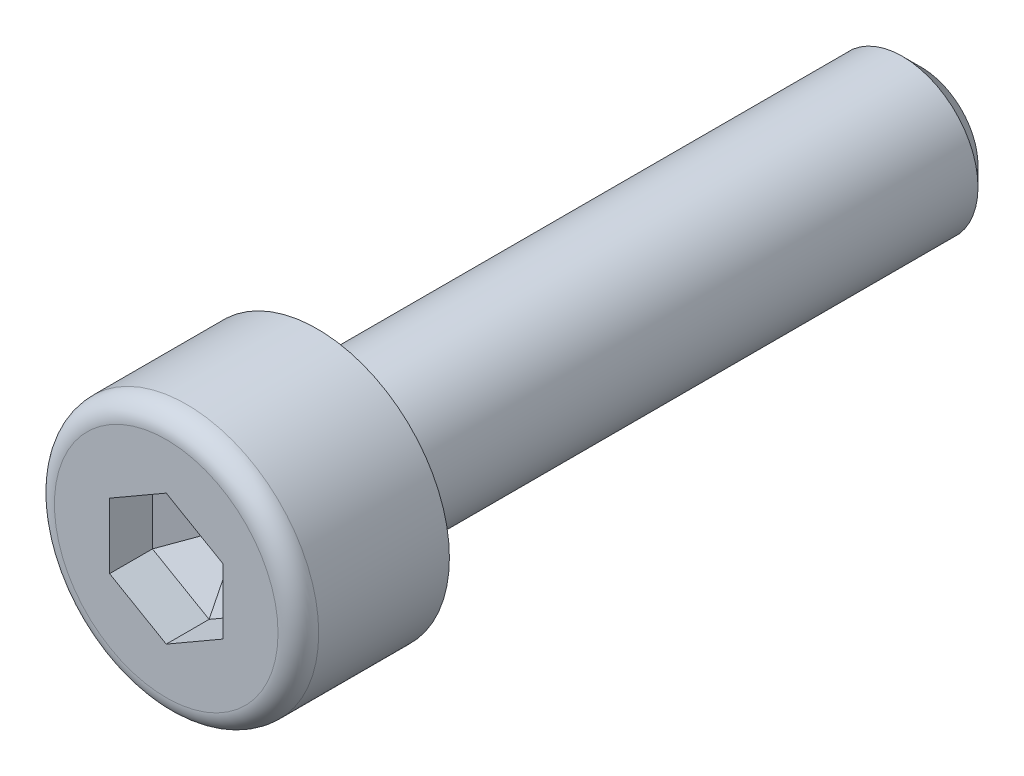
SolidWorks part; units mm, degrees
material "普通碳钢"
ref_plane "前视基准面" through (0, 0, 0) normal (0, 0, 1) x (1, 0, 0)
ref_plane "上视基准面" through (0, 0, 0) normal (0, 1, 0) x (1, 0, 0)
ref_plane "右视基准面" through (0, 0, 0) normal (1, 0, 0) x (0, 0, -1)
sketch "草图1" plane through (0, 0, 0) normal (0, 0, 1) x (1, 0, 0)
  circle A0 centre (0, 0) radius 3.5
  dimension "dk" = 7
extrude "凸台-拉伸1" add sketch "草图1" along normal blind 4
ref_axis "基准轴1" through (0, 0, 4) along (0, 0, -1)
sketch "草图2" plane through (0, 0, 4) normal (0, 0, 1) x (1, 0, 0)
  line L1 (1.5, 0.866) -> (0, 1.7321)
  line L2 (0, 1.7321) -> (-1.5, 0.866)
  line L3 (-1.5, 0.866) -> (-1.5, -0.866)
  line L4 (-1.5, -0.866) -> (0, -1.7321)
  line L5 (0, -1.7321) -> (1.5, -0.866)
  line L6 (1.5, -0.866) -> (1.5, 0.866)
  circle A0 centre (0, 0) radius 1.5 construction
  dimension "s" = 3
extrude "切除-拉伸1" cut sketch "草图2" against normal blind 2
sketch "草图3" plane through (0, 0, 0) normal (0, 0, -1) x (-1, 0, 0)
  circle A0 centre (0, 0) radius 2
  dimension "d" = 4
extrude "凸台-拉伸2" add sketch "草图3" along normal blind 16
cosmetic thread "装饰螺纹线1" parameters "b"=4.9, "D2"=1.221
chamfer "倒角1" distance 0.5 angle 45 1 edges at (-2, 0, -16)
fillet "圆角1" radius 0.5385 1 edges at (3.5, 0, 4)
chamfer "倒角2" distance 0.8646 angle 60 6 edges at (-1.5, 0, 2) (-0.75, 1.299, 2) (0.75, 1.299, 2) (1.5, 0, 2) (-0.75, -1.299, 2) (0.75, -1.299, 2) first distance on face at (-1.5, 0, 3) first distance on face at (-0.75, 1.299, 3) first distance on face at (0.75, 1.299, 3) first distance on face at (1.5, 0, 3) first distance on face at (-0.75, -1.299, 3) first distance on face at (0.75, -1.299, 3)
fillet "圆角2" radius 0.1 1 edges at (2, 0, 0)
ref_plane "基准面1" through (0, 0, 0) normal (0, 0, -1) x (-1, 0, 0)
equation "\"D1@倒角2\" = \"s@草图2\" / 3.47"
equation "\"D1@圆角1\"= \"dk@草图1\" / 13"
equation "\"D1@倒角1\"= \"d@草图3\" / 8"
equation "\"D1@圆角2\"= \"d@草图3\" / \"d@草图3\" * 0.1"
